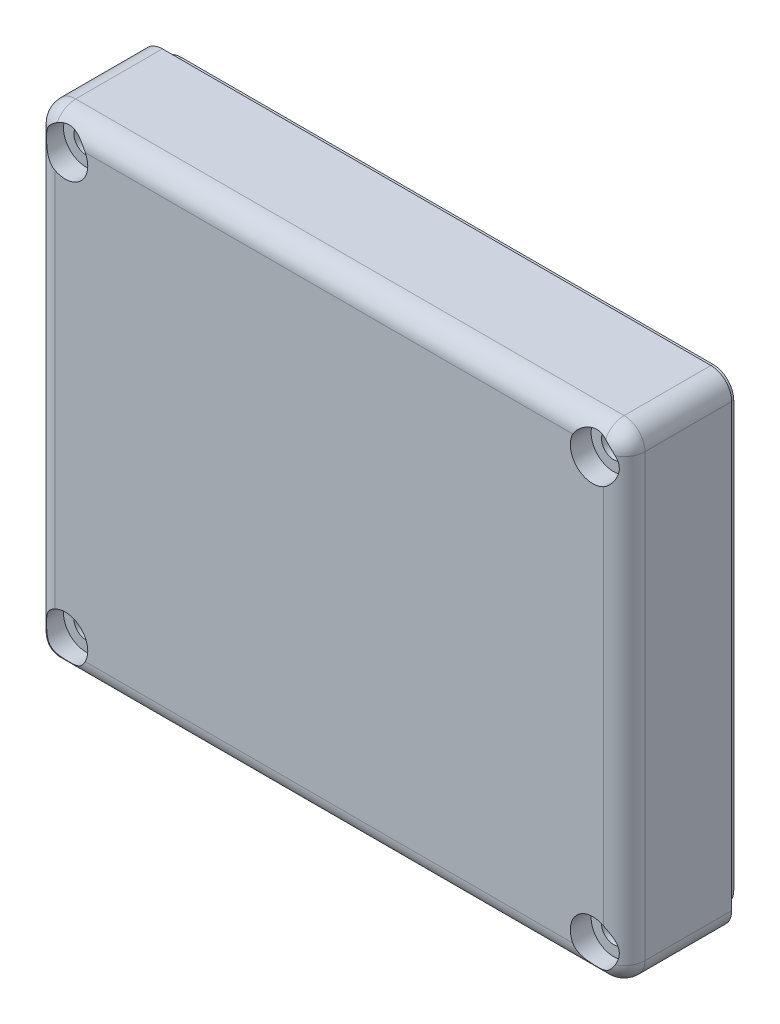
SolidWorks part; units mm, degrees
ref_plane "Plan de face" through (0, 0, 0) normal (0, 0, 1) x (1, 0, 0)
ref_plane "Plan de dessus" through (0, 0, 0) normal (0, 1, 0) x (1, 0, 0)
ref_plane "Plan de droite" through (0, 0, 0) normal (1, 0, 0) x (0, 0, -1)
sketch "Esquisse1" plane through (0, 0, 0) normal (0, 0, 1) x (1, 0, 0)
  line L1 (0, 0) -> (85, 0)
  line L2 (0, 0) -> (0, -69.5)
  line L3 (0, -69.5) -> (85, -69.5)
  line L4 (85, 0) -> (85, -69.5)
extrude "Boss.-Extru.1" add sketch "Esquisse1" along normal blind 2
sketch "Esquisse5" plane through (0, 0, 0) normal (0, 0, -1) x (-1, 0, 0)
  line L1 (-85, 0) -> (0, 0)
  line L2 (-85, 0) -> (-85, -69.5)
  line L3 (-85, -69.5) -> (0, -69.5)
  line L4 (0, 0) -> (0, -69.5)
  line L5 (-83, -2) -> (-2, -2)
  line L6 (-83, -2) -> (-83, -67.5)
  line L7 (-83, -67.5) -> (-2, -67.5)
  line L8 (-2, -2) -> (-2, -67.5)
  dimension "D1" = 2
  dimension "D2" = 2
  dimension "D3" = 2
  dimension "D4" = 2
extrude "Boss.-Extru.3" add sketch "Esquisse5" along normal blind 15
fillet "Congé1" radius 3 8 edges at (42.5, -69.5, 2) (85, -69.5, -6.5) (0, -69.5, -6.5) (85, 0, -6.5) (85, -34.75, 2) (0, 0, -6.5) (42.5, 0, 2) (0, -34.75, 2)
fillet "Congé2" radius 1.75 4 edges at (2, -67.5, -7.5) (2, -2, -7.5) (83, -2, -7.5) (83, -67.5, -7.5)
sketch "Esquisse13" plane through (0, 0, 0) normal (0, 0, -1) x (-1, 0, 0)
  line L0 (-85, -3) -> (-85, -66.5) construction
  line L1 (-3, 0) -> (-82, 0) construction
  line L2 (-81, -8) -> (-85, -8)
  line L3 (-85, -3) -> (-85, -66.5) construction
  line L4 (-85, -4) -> (-85, -8)
  line L6 (-81, 0) -> (-77, 0)
  line L7 (-3, 0) -> (-82, 0) construction
  line L8 (-77, 0) -> (-77, -4)
  circle A0 centre (-81, -4) radius 4
  line M18 (-3.75, -2) -> (-81.25, -2)
  arc M19 (-81.25, -2) -> (-83, -3.75) centre (-81.25, -3.75) ccw
  line M20 (-83, -3.75) -> (-83, -65.75)
  dimension "D1" = 4
  dimension "D2" = 4
extrude "Boss.-Extru.7" add sketch "Esquisse13" along normal up to surface (15 mm away) contours A0 M18 M19 M20 | A0 L8 M18 | A0 L2 M20 region at (80.1805, -4.8195, 0) region at (82.5069, -7.8413, 0) region at (77.1587, -2.4931, 0) up to face at (42.5, -34.75, -15)
ref_plane "Plan1" through (0, -34.75, 0) normal (0, 1, 0) x (1, 0, 0)
ref_plane "Plan2" through (42.5, 0, 0) normal (-1, 0, 0) x (0, 0, 1)
sketch "Esquisse14" plane through (0, 0, -15) normal (0, 0, -1) x (-1, 0, 0)
  line L2 (-85, -3) -> (-85, -66.5) construction
  line L3 (-3, 0) -> (-82, 0) construction
  circle A0 centre (-80.5, -4.5) radius 2.5 construction
  circle A2 centre (-80.5, -4.5) radius 1.75
  dimension "D1" = 5
  dimension "D3" = 4.5
  dimension "D2" = 4.5
extrude "Enlèv. mat.-Extru.11" cut sketch "Esquisse14" against normal blind 23
sketch "Esquisse23" plane through (0, 0, 2) normal (0, 0, 1) x (1, 0, 0)
  circle A0 centre (80.5, -4.5) radius 3.25
extrude "Enlèv. mat.-Extru.17" cut sketch "Esquisse23" against normal blind 3
mirror "Symétrie4" about plane through (0, -34.75, 0) normal (0, 1, 0) of "Enlèv. mat.-Extru.17", "Enlèv. mat.-Extru.11", "Boss.-Extru.7"
mirror "Symétrie5" about plane through (42.5, 0, 0) normal (-1, 0, 0) of "Symétrie4"
sketch "Esquisse21" plane through (0, 0, -15) normal (0, 0, -1) x (-1, 0, 0)
  line L0 (-82, -69.5) -> (-3, -69.5) construction
  line L1 (-80.8, -1.2) -> (-4.2, -1.2)
  line L2 (-83.8, -4.2) -> (-83.8, -65.3)
  line L3 (-80.8, -68.3) -> (-4.2, -68.3)
  line L4 (-1.2, -4.2) -> (-1.2, -65.3)
  line L5 (0, -66.5) -> (0, -3) construction
  line L6 (-3, 0) -> (-82, 0) construction
  line L7 (-85, -3) -> (-85, -66.5) construction
  line L9 (-82, 0) -> (-3, 0)
  line L10 (-85, -3) -> (-85, -66.5)
  line L11 (-82, -69.5) -> (-3, -69.5)
  line L12 (0, -3) -> (0, -66.5)
  arc A0 (-1.2, -4.2) -> (-4.2, -1.2) centre (-4.2, -4.2) ccw
  arc A1 (-4.2, -68.3) -> (-1.2, -65.3) centre (-4.2, -65.3) ccw
  arc A2 (-80.8, -68.3) -> (-83.8, -65.3) centre (-80.8, -65.3) cw
  arc A3 (-80.8, -1.2) -> (-83.8, -4.2) centre (-80.8, -4.2) ccw
  arc A4 (0, -3) -> (-3, 0) centre (-3, -3) ccw
  arc A5 (-3, -69.5) -> (0, -66.5) centre (-3, -66.5) ccw
  arc A6 (-82, -69.5) -> (-85, -66.5) centre (-82, -66.5) cw
  arc A7 (-85, -3) -> (-82, 0) centre (-82, -3) cw
  dimension "D5" = 3
  dimension "D10" = 3
  dimension "D1" = 1.2
  dimension "D2" = 1.2
  dimension "D3" = 1.2
  dimension "D4" = 1.2
  dimension "D6" = 1.2
  dimension "D7" = 1.2
  dimension "D8" = 1.2
  dimension "D9" = 1.2
extrude "Enlèv. mat.-Extru.15" cut sketch "Esquisse21" against normal blind 1.5
sketch "Esquisse24" plane through (0, 0, 0) normal (0, 0, -1) x (-1, 0, 0)
  line L0 (-80.5, -9.5) -> (-83, -9.5)
  line L1 (-75.5, -4.5) -> (-75.5, -2)
  line L2 (-8, -2) -> (-77, -2) construction
  line L3 (-83, -8) -> (-83, -61.5) construction
  line L4 (-83, -9.5) -> (-84.9229, -9.5)
  circle A0 centre (-80.5, -4.5) radius 5
  circle A1 centre (-80.5, -4.5) radius 3.2929
  line M4 (-8, -2) -> (-77, -2)
  line M5 (-77, -2) -> (-77, -4)
  arc M6 (-77, -4) -> (-81, -8) centre (-81, -4) cw
  line M7 (-81, -8) -> (-83, -8)
  line M8 (-83, -8) -> (-83, -61.5)
  dimension "D1" = 10
extrude "Boss.-Extru.8" add sketch "Esquisse24" along normal blind 3 contours A0 M4 M5 M6 M7 M8 | A0 L1 M4 | A0 L0 M8 region at (81.7666, -9.2272, 0) region at (82.3837, -9.3016, 0) region at (75.6984, -2.6163, 0)
fillet "Congé3" radius 0.75 9 edges at (81.75, -9.5, -3) (76.9645, -8.0355, -3) (77, -3, -3) (82, -8, -3) (81.75, -9.5, 0) (75.5, -3.25, 0) (75.5, -3.25, -3) (78.1716, -6.8284, -3) (76.9645, -8.0355, 0)
